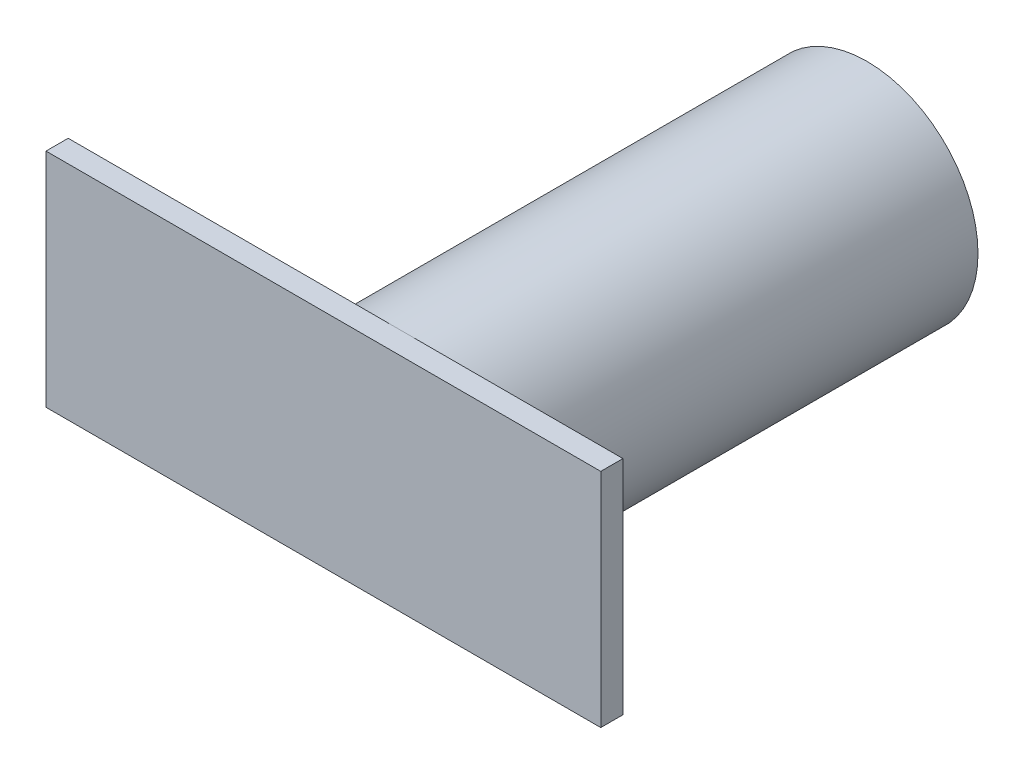
SolidWorks part; units mm, degrees
ref_plane "Front Plane" through (0, 0, 0) normal (0, 0, 1) x (1, 0, 0)
ref_plane "Top Plane" through (0, 0, 0) normal (0, 1, 0) x (1, 0, 0)
ref_plane "Right Plane" through (0, 0, 0) normal (1, 0, 0) x (0, 0, -1)
sketch "Sketch1" plane through (0, 0, 0) normal (0, 0, 1) x (1, 0, 0)
  line L1 (-10, -10) -> (10, -10)
  line L2 (-10, -10) -> (-10, 10)
  line L3 (-10, 10) -> (10, 10)
  line L4 (10, -10) -> (10, 10)
  line L5 (-10, -10) -> (10, 10) construction
  line L6 (-10, 10) -> (10, -10) construction
  point P0 (0, 0)
ref_plane "Plane1" through (0, 0, 5) normal (0, 0, 1) x (1, 0, 0)
sketch "Sketch2" plane through (0, 0, 5) normal (0, 0, 1) x (1, 0, 0)
  line L0 (-4, 4.1502) -> (-4, -4.1502)
  line L1 (-3.2572, -4.5873) -> (4.2133, -0.4371)
  line L2 (4.2133, 0.4371) -> (-3.2572, 4.5873)
  arc A0 (4.2133, -0.4371) -> (4.2133, 0.4371) centre (3.9704, 0) ccw
  arc A1 (-3.2572, -4.5873) -> (-4, -4.1502) centre (-3.5, -4.1502) cw
  arc A2 (-4, 4.1502) -> (-3.2572, 4.5873) centre (-3.5, 4.1502) cw
  dimension "D1" = 0.5
sketch "Sketch4" plane through (0, 0, 5) normal (0, 0, 1) x (1, 0, 0)
  line L1 (-3, 1) -> (2, 1)
  line L2 (-3, 1) -> (-3, -1)
  line L3 (-3, -1) -> (2, -1)
  line L4 (2, 1) -> (2, -1)
sketch "Sketch6" plane through (0, 0, 5) normal (0, 0, 1) x (1, 0, 0)
  circle A0 centre (0, 0) radius 0.75
  circle A1 centre (0, 0) radius 1
extrude "Boss-Extrude3" add sketch "Sketch4" along normal blind 0.2
extrude "Boss-Extrude4" add sketch "Sketch6" against normal blind 4.2 contours A1
sketch "Sketch7" plane through (0, 0, 5) normal (0, 0, 1) x (1, 0, 0)
  circle A0 centre (0, 0) radius 0.75
  circle A1 centre (0, 0) radius 1
extrude "Cut-Extrude2" cut sketch "Sketch7" against normal blind 4.2 contours A0
